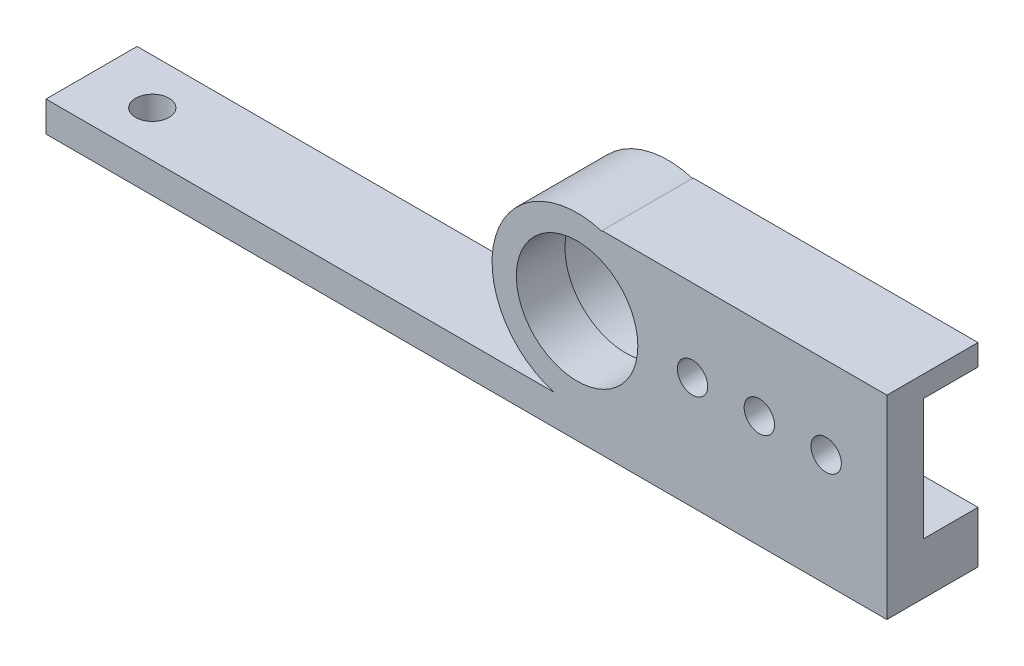
SolidWorks part; units mm, degrees
ref_plane "前视基准面" through (0, 0, 0) normal (0, 0, 1) x (1, 0, 0)
ref_plane "上视基准面" through (0, 0, 0) normal (0, 1, 0) x (1, 0, 0)
ref_plane "右视基准面" through (0, 0, 0) normal (1, 0, 0) x (0, 0, -1)
sketch "草图1" plane through (0, 0, 0) normal (0, 0, 1) x (1, 0, 0)
  line L1 (20, -10) -> (-20, -10)
  line L2 (20, -10) -> (20, 10)
  line L3 (20, 10) -> (-20, 10)
  line L4 (-20, -10) -> (-20, 10)
  line L5 (20, -10) -> (-20, 10) construction
  line L6 (20, 10) -> (-20, -10) construction
  point P0 (0, 0)
  dimension "D1" = 40
  dimension "D2" = 20
extrude "凸台-拉伸1" add sketch "草图1" along normal blind 6
sketch "草图2" plane through (0, 0, 6) normal (0, 0, 1) x (1, 0, 0)
  line L0 (20, -10) -> (20, 10) construction
  circle A0 centre (10, 0) radius 2.5
  circle A1 centre (-1, 0) radius 2.5
  circle A2 centre (-12, 0) radius 2.5
  dimension "D1" = 10
  dimension "D2" = 5
  dimension "D3" = 3
extrude "切除-拉伸1" cut sketch "草图2" against normal through all
sketch "草图3" plane through (0, 0, 6) normal (0, 0, 1) x (1, 0, 0)
  line L0 (20, 13.5) -> (20, 10)
  line L1 (20, -13.5) -> (-26.894, -13.5)
  line L3 (20, 13.5) -> (-26.894, 13.5)
  line L4 (-20, 10) -> (-20, -10)
  line L5 (-20, -10) -> (20, -10)
  line L6 (20, -10) -> (20, 10)
  line L7 (20, 10) -> (-20, 10)
  line L8 (-20, 10) -> (-20, -10)
  line L9 (-20, -10) -> (20, -10)
  line L10 (20, -10) -> (20, 10)
  line L11 (20, 10) -> (-20, 10)
  line L12 (-26.894, -13.5) -> (-26.894, 13.5)
  line L13 (20, -10.0394) -> (-26.894, 13.5) construction
  line L14 (20, 10.0394) -> (-26.894, -13.5) construction
  line L15 (20, -10) -> (20, -13.5)
  circle A0 centre (-31, 0) radius 11
  circle A1 centre (-31, 0) radius 14
  point P2 (0, 0)
  line M10 (-20, 10) -> (-20, -10)
  line M11 (-20, -10) -> (20, -10)
  line M13 (20, 10) -> (-20, 10)
  dimension "D3" = 22
  dimension "D4" = 28
  dimension "D2" = 3.5
  dimension "D1" = 0
extrude "凸台-拉伸2" add sketch "草图3" against normal blind 15 contours L3 A1 L1 L12 A0 | A1 L1 L15 M11 M10 | L1 A1 L8 A0 L12 | L8 A1 L3 L12 A0 | L8 A1 | A1 L0 L3 M10 M13 region at (-1.9449, 11.7771, 6) region at (-1.9449, -11.7771, 6) region at (-23.0173, 9.0328, 6) region at (-27.2274, 11.7946, 6) region at (-18.7882, 0, 6) region at (-23.0173, -9.0328, 6)
sketch "草图5" plane through (0, 0, 6) normal (0, 0, 1) x (1, 0, 0)
  circle A0 centre (-31, 0) radius 10
  circle A1 centre (-31, 0) radius 11 construction
  circle A2 centre (-31, 0) radius 11
  dimension "D1" = 20
extrude "凸台-拉伸3" add sketch "草图5" against normal blind 8
sketch "草图6" plane through (0, 0, 6) normal (0, 0, 1) x (1, 0, 0)
  circle A0 centre (-31, 0) radius 8.5
  circle A1 centre (-31, 0) radius 10 construction
  circle A2 centre (-31, 0) radius 10
  dimension "D1" = 17
sketch "草图9" plane through (0, -13.5, 0) normal (0, -1, 0) x (1, 0, 0)
  circle A0 centre (-18.2368, -1.344) radius 5.5352
sketch "草图10" plane through (20, 0, 0) normal (1, 0, 0) x (0, 0, -1)
  line L1 (9, -13.5) -> (-6, -13.5)
  line L2 (9, -13.5) -> (9, -18.5)
  line L3 (9, -18.5) -> (-6, -18.5)
  line L4 (-6, -13.5) -> (-6, -18.5)
  dimension "D1" = 5
extrude "凸台-拉伸4" add sketch "草图10" against normal blind 200
sketch "草图11" plane through (0, 0, 6) normal (0, 0, 1) x (1, 0, 0)
  line L1 (-28.6193, -11.8661) -> (-25.5243, -11.8661)
  line L2 (-28.6193, -11.8661) -> (-28.6193, -14.961)
  line L3 (-28.6193, -14.961) -> (-25.5243, -14.961)
  line L4 (-25.5243, -11.8661) -> (-25.5243, -14.961)
extrude "凸台-拉伸5" add sketch "草图11" against normal through all
sketch "草图13" plane through (0, -18.5, 0) normal (0, -1, 0) x (1, 0, 0)
  line L0 (-164.0842, 6) -> (-164.0842, -9)
  line L1 (-180, 6) -> (20, 6) construction
  line L2 (-164.0842, 123.2983) -> (-164.0842, -246.7017) construction
  line L3 (-180, -9) -> (20, -9) construction
sketch "草图14" plane through (0, -18.5, 0) normal (0, -1, 0) x (1, 0, 0)
  line L0 (-118.4338, -15.7251) -> (-118.4338, 9.3691)
  line L1 (-118.4338, 121.5018) -> (-118.4338, -248.4982) construction
sketch "草图15" plane through (0, -18.5, 0) normal (0, -1, 0) x (1, 0, 0)
  line L1 (-118.4338, -15.7251) -> (-184.1416, -15.7251)
  line L2 (-118.4338, -15.7251) -> (-118.4338, 11.9644)
  line L3 (-118.4338, 11.9644) -> (-184.1416, 11.9644)
  line L4 (-184.1416, -15.7251) -> (-184.1416, 11.9644)
sketch "草图16" plane through (0, -18.5, 0) normal (0, -1, 0) x (1, 0, 0)
  line L0 (-118.4338, -17.1171) -> (-118.4338, 37.1771)
  line L1 (-118.4338, 121.5018) -> (-118.4338, -248.4982) construction
sketch "草图17" plane through (0, -18.5, 0) normal (0, -1, 0) x (1, 0, 0)
  line L1 (-118.4338, -17.1171) -> (-191.9094, -17.1171)
  line L2 (-118.4338, -17.1171) -> (-118.4338, 25.2398)
  line L3 (-118.4338, 25.2398) -> (-191.9094, 25.2398)
  line L4 (-191.9094, -17.1171) -> (-191.9094, 25.2398)
extrude "切除-拉伸2" cut sketch "草图17" against normal through all
sketch "草图18" plane through (0, -18.5, 0) normal (0, -1, 0) x (1, 0, 0)
  line L0 (-111.5853, 6) -> (-111.5853, -9)
  line L1 (-118.4338, 6) -> (20, 6) construction
  line L2 (-118.4338, -9) -> (20, -9) construction
  line L3 (-118.4338, -1.5) -> (-108.4338, -1.5)
  line L4 (-118.4338, -15.7251) -> (-118.4338, 9.3691) construction
  circle A0 centre (-108.4338, -1.5) radius 2.75
  dimension "D2" = 5.5
  dimension "D1" = 10
extrude "切除-拉伸3" cut sketch "草图18" against normal blind 10 contours A0
